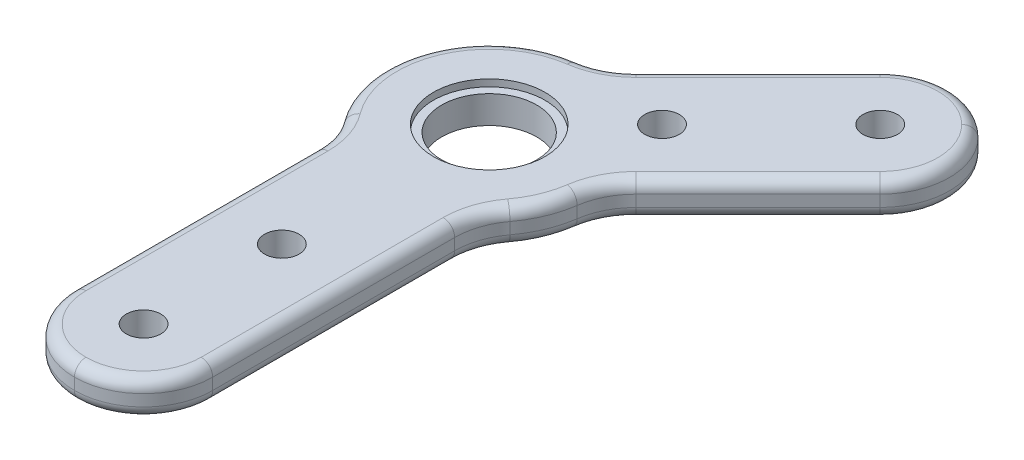
SolidWorks part; units mm, degrees
material "6061 Alloy"
ref_plane "Front Plane" through (0, 0, 0) normal (0, 0, 1) x (1, 0, 0)
ref_plane "Top Plane" through (0, 0, 0) normal (0, 1, 0) x (1, 0, 0)
ref_plane "Right Plane" through (0, 0, 0) normal (1, 0, 0) x (0, 0, -1)
sketch "Sketch1" plane through (0, 0, 0) normal (0, 1, 0) x (1, 0, 0)
  line L0 (0, 44.45) -> (0, -44.45) construction
  line L1 (-12.7, -44.45) -> (12.7, -44.45)
  line L2 (-12.7, -44.45) -> (-12.7, 31.75)
  line L3 (-12.7, 44.45) -> (12.7, 44.45) construction
  line L4 (12.7, -44.45) -> (12.7, 31.75)
  line L5 (-12.7, -44.45) -> (12.7, 44.45) construction
  line L6 (-12.7, 44.45) -> (12.7, -44.45) construction
  line L7 (0, 31.75) -> (44.9013, 76.6513) construction
  line L8 (8.9803, 22.7697) -> (53.8815, 67.671)
  line L9 (53.8815, 67.671) -> (35.921, 85.6315)
  line L10 (35.921, 85.6315) -> (-8.9803, 40.7303)
  line L11 (-8.9803, 40.7303) -> (8.9803, 22.7697) construction
  line L12 (12.7, 44.45) -> (12.7, 31.75) construction
  line L13 (12.7, 44.45) -> (12.7, 62.4105) construction
  circle A0 centre (0, 31.75) radius 12.7 construction
  circle A1 centre (0, -31.75) radius 3.175
  circle A2 centre (0, -6.35) radius 3.175
  circle A3 centre (0, 31.75) radius 8.7312
  circle A4 centre (35.921, 67.671) radius 3.175
  circle A5 centre (15.875, 47.625) radius 3.175
  circle A6 centre (0, 31.75) radius 19.05
  point P0 (0, 0)
  point P16 (44.9013, 76.6513)
  point P21 (0, 31.75)
  dimension "D4" = 12.7
  dimension "D1" = 6.35
  dimension "D7" = 50.8
  dimension "D8" = 12.7
  dimension "D9" = 17.4625
  dimension "D10" = 6.35
  dimension "D2" = 25.4
  dimension "D3" = 45
  dimension "D5" = 25.4
  dimension "D6" = 38.1
extrude "Boss-Extrude1" add sketch "Sketch1" along normal blind 6.35 contours A0 L2 L1 L4 L8 A2 A1 | A0 A3 | A0 L4 L8 L9 L10 A4 | A0 L8 L4 | L4 A6 L8 region at (0, 0, 14.9202) region at (-17.1023, 0, -38.834) region at (15.553, 0, -25.3078) region at (28.7883, 0, -60.5383)
fillet "Fillet2" radius 12.7 8 edges at (35.921, 3.175, -85.6315) (53.8815, 3.175, -67.671) (-12.7, 3.175, 44.45) (12.7, 3.175, 44.45) (1.06, 3.175, -50.7705) (-12.7, 3.175, -17.551) (12.7, 3.175, -17.551) (19.0205, 3.175, -32.81)
fillet "Fillet3" radius 2.1167 28 edges at (12.7, 0, 9.525) (8.9803, 0, 40.7303) (-8.9803, 0, 40.7303) (-12.7, 0, 9.525) (15.7154, 0, -65.426) (35.921, 0, -80.371) (48.621, 0, -67.671) (12.7, 6.35, 9.525) (8.9803, 6.35, 40.7303) (-8.9803, 6.35, 40.7303) (-12.7, 6.35, 9.525) (15.7154, 6.35, -65.426) (35.921, 6.35, -80.371) (48.621, 6.35, -67.671) (33.676, 0, -47.4654) (33.676, 6.35, -47.4654) (-13.3517, 0, -16.7161) (-17.5999, 0, -39.0401) (1.1895, 0, -51.8217) (-13.3517, 6.35, -16.7161) (-17.5999, 6.35, -39.0401) (1.1895, 6.35, -51.8217) (20.0717, 0, -32.9395) (17.5999, 0, -24.4599) (13.3517, 0, -16.7161) (20.0717, 6.35, -32.9395) (17.5999, 6.35, -24.4599) (13.3517, 6.35, -16.7161)
sketch "Sketch2" plane through (0, 6.35, 0) normal (0, 1, 0) x (1, 0, 0)
  circle A0 centre (0, 31.75) radius 10.2489
  dimension "D1" = 20.4978
extrude "Cut-Extrude1" cut sketch "Sketch2" against normal blind 1.27
